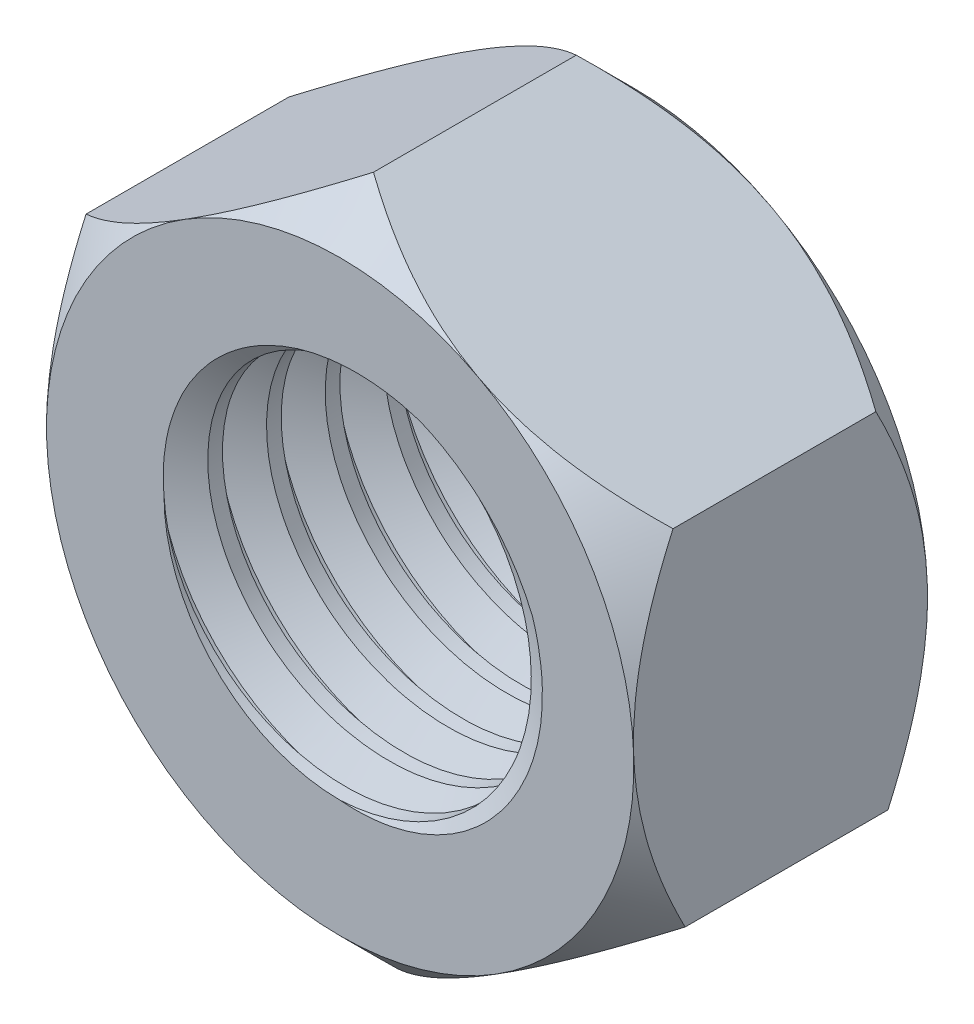
SolidWorks part; units mm, degrees
ref_plane "Front Plane" through (0, 0, 0) normal (0, 0, 1) x (1, 0, 0)
ref_plane "Top Plane" through (0, 0, 0) normal (0, 1, 0) x (1, 0, 0)
ref_plane "Right Plane" through (0, 0, 0) normal (1, 0, 0) x (0, 0, -1)
sketch "Sketch1" plane through (0, 0, 0) normal (0, 0, 1) x (1, 0, 0)
  line L1 (5.1, -2.7061) -> (4.8936, 3.0637)
  line L2 (4.8936, 3.0637) -> (-0.2064, 5.7698)
  line L3 (-0.2064, 5.7698) -> (-5.1, 2.7061)
  line L4 (-5.1, 2.7061) -> (-4.8936, -3.0637)
  line L5 (-4.8936, -3.0637) -> (0.2064, -5.7698)
  line L6 (0.2064, -5.7698) -> (5.1, -2.7061)
  circle A0 centre (0, 0) radius 5 construction
  circle A1 centre (0, 0) radius 3
  dimension "D2" = 6
  dimension "D1" = 5
extrude "Boss-Extrude1" add sketch "Sketch1" along normal mid plane 5 contours A1 | L5 L6 L1 L2 L3 L4 A1
sketch "Sketch3" plane through (0, 0, 2.5) normal (0, 0, 1) x (1, 0, 0)
  circle A0 centre (0, 0) radius 3
  dimension "D1" = 6
sketch "Sketch4" plane through (0, 0, 2.5) normal (0, 0, 1) x (1, 0, 0)
  circle A0 centre (0, 0) radius 5
  dimension "D1" = 10
extrude "Cut-Extrude2" cut sketch "Sketch4" against normal blind 16 draft 45 flip side to cut
mirror "Mirror2" about plane through (0, 0, 0) normal (0, 0, 1) of "Cut-Extrude2"
extrude "Cut-Extrude4" cut sketch "Sketch3" against normal blind 26
thread "Thread3" start angle 0, offset 3, length 0, pitch 1, diameter 6
ref_plane "Plane4" through (-3, 0, 5.5) normal (0, -1, 0) x (-1, 0, 0)
sketch "Thread Profile4" plane through (-3, 0, 5.5) normal (0, -1, 0) x (-1, 0, 0)
  line L0 (0, 0) -> (0, 1) construction
  line L1 (0, 0) -> (0.5413, 0.3125)
  line L2 (0.5413, 0.3125) -> (0.5413, 0.4375)
  line L3 (0.5413, 0.4375) -> (0, 0.75)
  line L4 (0.5413, 0.375) -> (0, 0.375) construction
  line L11 (0, 0) -> (0, 0.75)
  point P2 (0, 0)
  dimension "Pitch" = 1
  dimension "Profile_Angle" = 60
  dimension "Profile_Land" = 0.125
  dimension "Profile_Height" = 0.5413
